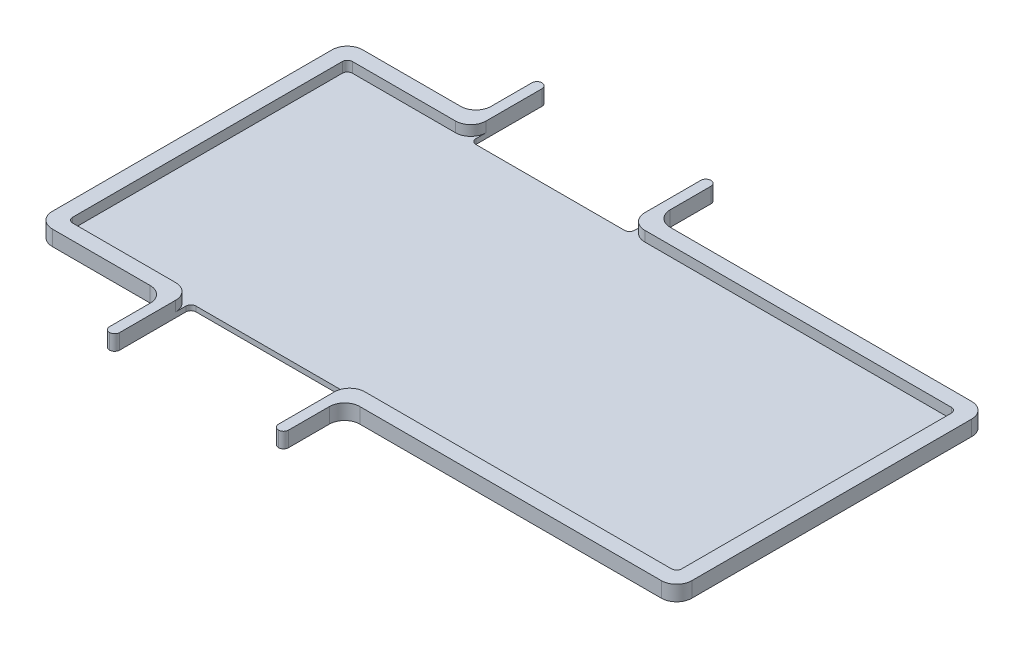
SolidWorks part; units mm, degrees
ref_plane "Front Plane" through (0, 0, 0) normal (0, 0, 1) x (1, 0, 0)
ref_plane "Top Plane" through (0, 0, 0) normal (0, 1, 0) x (1, 0, 0)
ref_plane "Right Plane" through (0, 0, 0) normal (1, 0, 0) x (0, 0, -1)
sketch "Sketch3" plane through (0, 0, 0) normal (0, 1, 0) x (1, 0, 0)
  line L0 (0, -27.5) -> (0, 27.5) construction
  line L1 (-59.85, -27.5) -> (59.85, -27.5)
  line L2 (-59.85, -27.5) -> (-59.85, 27.5)
  line L3 (-59.85, 27.5) -> (59.85, 27.5)
  line L4 (59.85, -27.5) -> (59.85, 27.5)
  line L5 (-59.85, -27.5) -> (59.85, 27.5) construction
  line L6 (-59.85, 27.5) -> (59.85, -27.5) construction
  line L7 (-59.85, 0) -> (59.85, 0) construction
  line L8 (-20, -27.5) -> (-20, 27.5) construction
  line L9 (-62.85, 30.5) -> (-37.6, 30.5)
  line L10 (62.85, -30.5) -> (62.85, 30.5)
  line L11 (-62.85, -30.5) -> (-37.6, -30.5)
  line L12 (-62.85, -30.5) -> (-62.85, 30.5)
  line L13 (-37.6, 30.5) -> (-37.6, 42.5)
  line L14 (-37.6, 42.5) -> (-35.6, 42.5)
  line L15 (-35.6, 42.5) -> (-35.6, 27.5)
  line L16 (-2.4, 42.5) -> (-4.4, 42.5)
  line L17 (-2.4, 30.5) -> (-2.4, 42.5)
  line L18 (-4.4, 42.5) -> (-4.4, 27.5)
  line L19 (-35.6, 27.5) -> (-59.85, 27.5)
  line L20 (-62.85, 30.5) -> (62.85, 30.5) construction
  line L21 (-2.4, 30.5) -> (62.85, 30.5)
  line L22 (-59.85, -27.5) -> (59.85, -27.5)
  line L23 (59.85, 27.5) -> (-4.4, 27.5)
  line L24 (-2.4, -30.5) -> (-2.4, -42.5)
  line L25 (-4.4, -42.5) -> (-4.4, -27.5)
  line L26 (-2.4, -42.5) -> (-4.4, -42.5)
  line L27 (-37.6, -42.5) -> (-35.6, -42.5)
  line L28 (-35.6, -42.5) -> (-35.6, -27.5)
  line L29 (-37.6, -30.5) -> (-37.6, -42.5)
  line L30 (-2.4, -30.5) -> (62.85, -30.5)
  line L31 (-62.85, -30.5) -> (62.85, -30.5) construction
  point P0 (0, 0)
  point P9 (0, 0)
  point P12 (0, 0)
  point P15 (-20, 0)
  dimension "D1" = 119.7
  dimension "D2" = 55
  dimension "D3" = 20
  dimension "D5" = 15.6
  dimension "D6" = 2
  dimension "D7" = 12
  dimension "D8" = 12
  dimension "D4" = 3
extrude "Boss-Extrude6" add sketch "Sketch3" along normal blind 3 contours L11 L29 L27 L28 L1 L2 L3 L15 L14 L13 L9 L12 | L24 L30 L10 L21 L17 L16 L18 L3 L4 L22 L25 L26 region at (-47.725, 0, 28.3926) region at (27.725, 0, 28.5839)
sketch "Sketch4" plane through (0, 0, 0) normal (0, 1, 0) x (1, 0, 0)
  line L1 (-59.85, 27.5) -> (59.85, 27.5)
  line L2 (-59.85, 27.5) -> (-59.85, -27.5)
  line L3 (-59.85, -27.5) -> (59.85, -27.5)
  line L4 (59.85, 27.5) -> (59.85, -27.5)
extrude "Boss-Extrude7" add sketch "Sketch4" along normal blind 1
fillet "Fillet13" radius 3 4 edges at (62.85, 1.5, -30.5) (62.85, 1.5, 30.5) (-62.85, 1.5, 30.5) (-62.85, 1.5, -30.5)
fillet "Fillet14" radius 1 4 edges at (59.85, 2, 27.5) (59.85, 2, -27.5) (-59.85, 2, -27.5) (-59.85, 2, 27.5)
fillet "Fillet15" radius 1 8 edges at (-2.4, 1.5, 42.5) (-4.4, 1.5, 42.5) (-35.6, 1.5, 42.5) (-37.6, 1.5, 42.5) (-35.6, 1.5, -42.5) (-37.6, 1.5, -42.5) (-2.4, 1.5, -42.5) (-4.4, 1.5, -42.5)
fillet "Fillet16" radius 3 4 edges at (-2.4, 1.5, -30.5) (-37.6, 1.5, -30.5) (-37.6, 1.5, 30.5) (-2.4, 1.5, 30.5)
fillet "Fillet17" radius 3 2 edges at (-35.6, 2, -27.5) (-4.4, 2, -27.5)
fillet "Fillet18" radius 1 2 edges at (-35.6, 0.5, -27.5) (-4.4, 0.5, -27.5)
fillet "Fillet19" radius 3 2 edges at (-4.4, 2, 27.5) (-35.6, 2, 27.5)
fillet "Fillet20" radius 1 2 edges at (-35.6, 0.5, 27.5) (-4.4, 0.5, 27.5)
